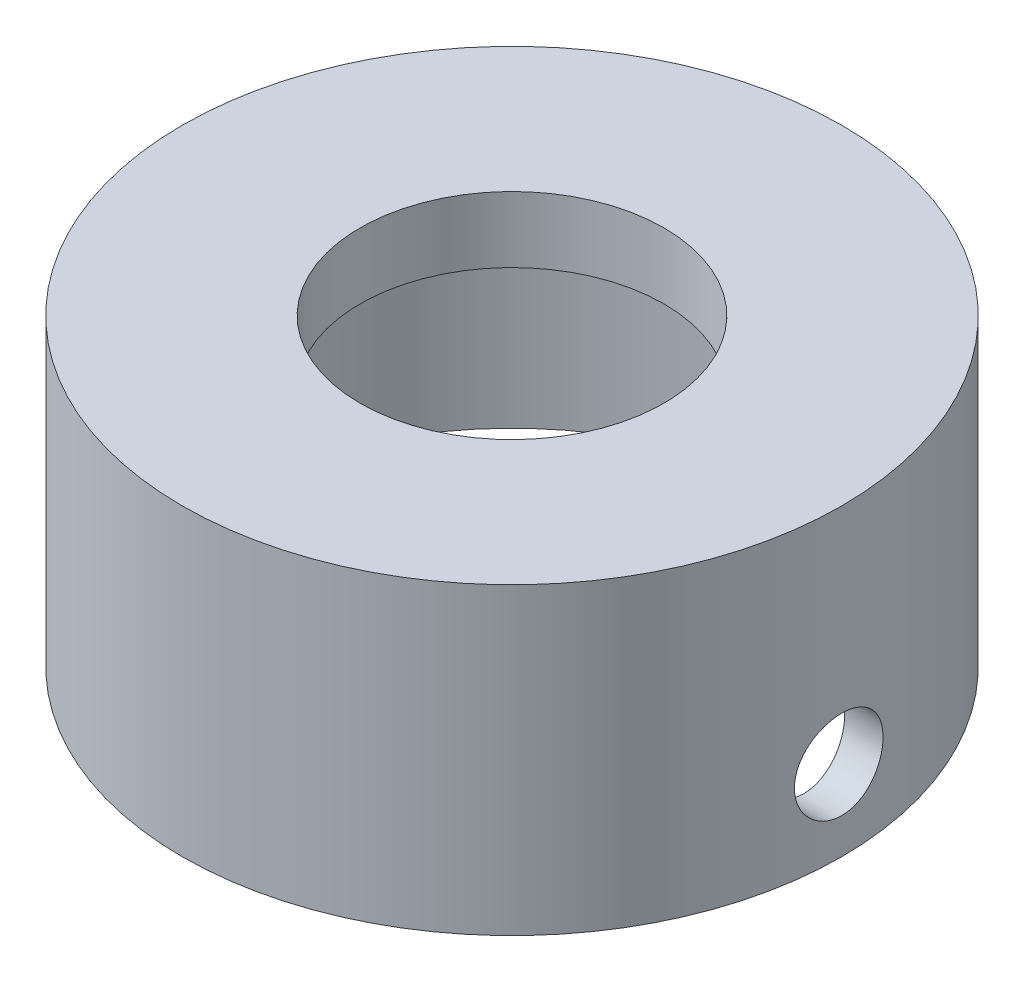
SolidWorks part; units mm, degrees
ref_plane "Front Plane" through (0, 0, 0) normal (0, 0, 1) x (1, 0, 0)
ref_plane "Top Plane" through (0, 0, 0) normal (0, 1, 0) x (1, 0, 0)
ref_plane "Right Plane" through (0, 0, 0) normal (1, 0, 0) x (0, 0, -1)
sketch "Sketch1" plane through (0, 0, 0) normal (0, 1, 0) x (1, 0, 0)
  circle A0 centre (0, 0) radius 20.6693
  dimension "D2" = 41.3385
extrude "Boss-Extrude1" add sketch "Sketch1" against normal blind 19.05
sketch "Sketch2" plane through (0, -19.05, 0) normal (0, -1, 0) x (1, 0, 0)
  circle A0 centre (0, 0) radius 18.288
  dimension "D1" = 36.576
extrude "Cut-Extrude1" cut sketch "Sketch2" against normal blind 13.3985
sketch "Sketch3" plane through (0, 0, 0) normal (0, 1, 0) x (1, 0, 0)
  circle A0 centre (0, 0) radius 9.525
  dimension "D1" = 19.05
extrude "Cut-Extrude2" cut sketch "Sketch3" against normal through all
sketch "Sketch4" plane through (0, -5.6515, 0) normal (0, -1, 0) x (1, 0, 0)
  circle A0 centre (0, 0) radius 15.875
  dimension "D1" = 31.75
extrude "Cut-Extrude3" cut sketch "Sketch4" against normal blind 1.524
sketch "Sketch5" plane through (0, 0, 0) normal (1, 0, 0) x (0, 0, -1)
  line L0 (-15.875, -4.1275) -> (15.875, -4.1275) construction
  circle A0 centre (0, -14.0335) radius 2.7781
  dimension "D1" = 5.5562
  dimension "D2" = 9.906
extrude "Cut-Extrude4" cut sketch "Sketch5" against normal through all and the other way through all
